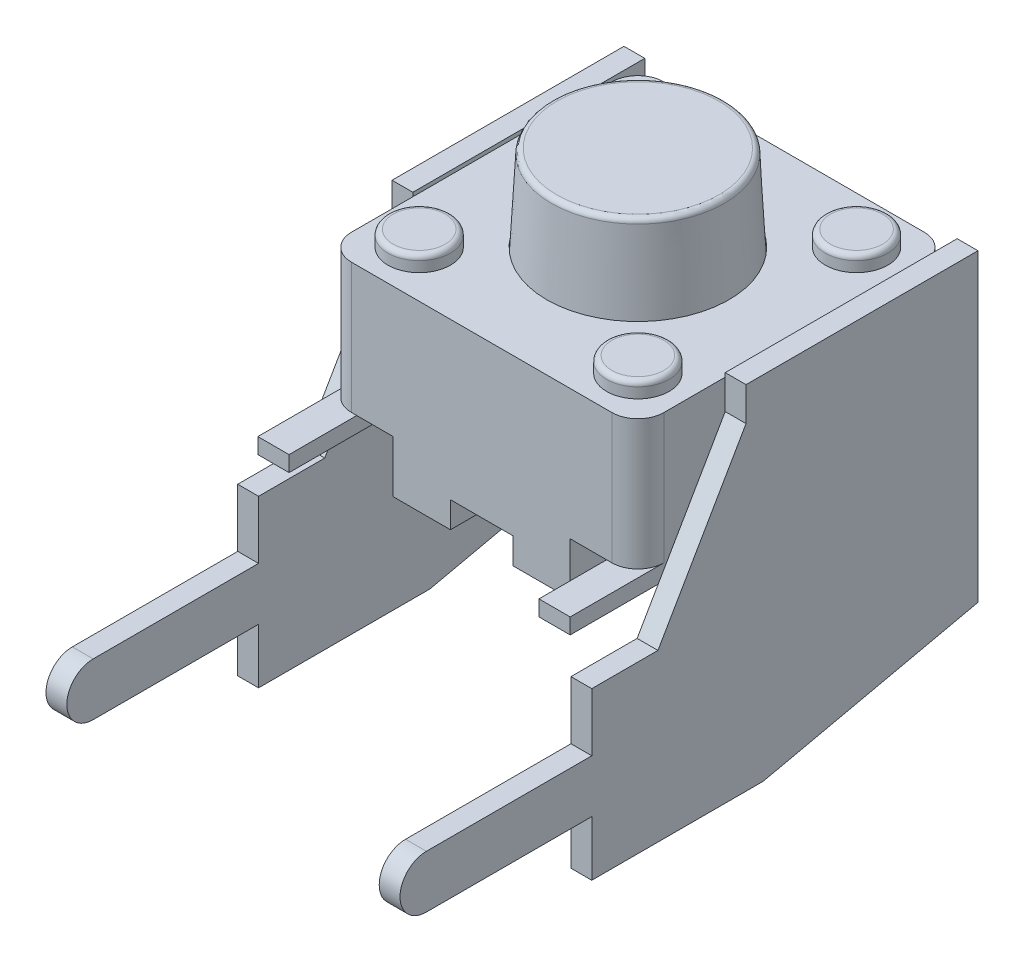
SolidWorks part; units mm, degrees
material "Custom Plastic"
ref_plane "Front Plane" through (0, 0, 0) normal (0, 0, 1) x (1, 0, 0)
ref_plane "Top Plane" through (0, 0, 0) normal (0, 1, 0) x (1, 0, 0)
ref_plane "Right Plane" through (0, 0, 0) normal (1, 0, 0) x (0, 0, -1)
sketch "Sketch1" plane through (0, 0, 0) normal (0, 1, 0) x (1, 0, 0)
  line L0 (-3.2652, 0) -> (3.207, 0) construction
  line L1 (-2.5, 3) -> (2.5, 3)
  line L2 (-3, 2.5) -> (-3, -2.5)
  line L3 (-2.5, -3) -> (2.5, -3)
  line L4 (3, 2.5) -> (3, -2.5)
  line L5 (-3, 3) -> (3, -3) construction
  line L6 (-3, -3) -> (3, 3) construction
  line L7 (0, -3.1905) -> (0, 3.2124) construction
  line L8 (3, 0) -> (2.4, 0)
  line L9 (3, 0) -> (3, -0.3)
  line L10 (3, -0.3) -> (2.4, -0.3)
  line L11 (2.4, 0) -> (2.4, -0.3)
  line L12 (-3, -0.3) -> (-2.4, -0.3)
  line L13 (-2.4, 0) -> (-2.4, -0.3)
  line L14 (-3, 0) -> (-2.4, 0)
  circle A0 centre (2.1, 2.1) radius 0.6
  circle A1 centre (2.1, -2.1) radius 0.6
  circle A2 centre (-2.1, -2.1) radius 0.6
  circle A3 centre (-2.1, 2.1) radius 0.6
  circle A4 centre (0, 0) radius 1.75
  arc A5 (2.5, 3) -> (3, 2.5) centre (2.5, 2.5) cw
  arc A6 (2.5, -3) -> (3, -2.5) centre (2.5, -2.5) ccw
  arc A7 (-3, -2.5) -> (-2.5, -3) centre (-2.5, -2.5) ccw
  arc A8 (-2.5, 3) -> (-3, 2.5) centre (-2.5, 2.5) ccw
  point P0 (0, 0)
  point P1 (0, 0)
  point P9 (0, 0)
  point P18 (0, 0)
  dimension "D1" = 6
  dimension "D2" = 0.9
  dimension "D3" = 1.2
  dimension "D5" = 3.5
  dimension "D6" = 0.5
  dimension "D7" = 0.6
  dimension "D8" = 0.3
  dimension "D4" = 4
extrude "Base" add sketch "Sketch1" along normal blind 3.3 contours L14 L2 L12 L13 | L1 A8 L2 L14 L13 L12 A7 L3 A6 L4 L10 L11 L8 A5 A0 A1 A2 A3 A4 | A3 | A2 | A4 | A1 | L8 L11 L10 L4 | A0 region at (0, 0, -2.9151) region at (-2.7, 0, 0.15) region at (2.7, 0, 0.15) region at (2.1, 0, -2.1) region at (2.1, 0, 2.1) region at (-2.1, 0, 2.1) region at (-2.1, 0, -2.1) region at (0, 0, 0)
extrude "Top Plate" add sketch "Sketch1<3>" along normal blind 0.2 from surface separate body contours L1 A8 L2 L14 L13 L12 A7 L3 A6 L4 L10 L11 L8 A5 A0 A1 A2 A3 A4 | L8 L11 L10 L4 | L14 L2 L12 L13 region at (0, 0, -2.9151) region at (-2.7, 0, 0.15) region at (2.7, 0, 0.15) starting at face at (0, 3.3, 0)
sketch "Sketch1<3>" plane through (0, 0, 0) normal (0, 1, 0) x (1, 0, 0) same geometry as "Sketch1"
extrude "Knobs" add sketch "Sketch1<4>" along normal blind 0.5 from offset 3.3 contours A1 | A2 | A3 | A0 region at (2.1, 0, -2.1) region at (2.1, 0, 2.1) region at (-2.1, 0, 2.1) region at (-2.1, 0, -2.1)
sketch "Sketch1<4>" plane through (0, 0, 0) normal (0, 1, 0) x (1, 0, 0) same geometry as "Sketch1"
extrude "Actuator" add sketch "Sketch1<5>" along normal blind 1.85 draft 3 from surface separate body contours A4 region at (0, 0, 0) starting at face at (-2.1, 3.3, -1.5)
sketch "Sketch1<5>" plane through (0, 0, 0) normal (0, 1, 0) x (1, 0, 0) same geometry as "Sketch1"
sketch "Sketch2" plane through (0, 0, 0) normal (0, -1, 0) x (1, 0, 0)
  line L0 (0, 3) -> (0.6, 3)
  line L1 (0, 3) -> (0, -3) construction
  line L2 (-2.5, 3) -> (2.5, 3) construction
  line L3 (0.6, 3) -> (1.7, 3)
  line L4 (0, -3) -> (0.6, -3)
  line L5 (-1.7, -2) -> (-3, -2)
  line L6 (0.6, -3) -> (0.6, 3)
  line L7 (-1.7, -0.9) -> (-1.7, -2)
  line L8 (-1.7, -0.9) -> (-3, -0.9)
  line L9 (1.7, -0.9) -> (3, -0.9)
  line L10 (1.7, -0.9) -> (1.7, -2)
  line L11 (-3, -0.4) -> (-1.7, -0.4)
  line L12 (-0.6, -3) -> (-0.6, 3)
  line L13 (1.7, 3) -> (1.7, -0.4)
  line L14 (-1.7, 3) -> (-1.7, -0.4)
  line L15 (3, 0) -> (-3, 0) construction
  line L16 (-3, -2.5) -> (-3, 2.5) construction
  line L21 (-2.5, -3) -> (2.5, -3) construction
  line L22 (1.7, -2) -> (3, -2)
  line L23 (3, -2.5) -> (3, 2.5) construction
  line L25 (3, -0.4) -> (1.7, -0.4)
  point P5 (0, 0)
  point P12 (0, 0)
  arc M1 (3, 2.5) -> (2.5, 3) centre (2.5, 2.5) ccw
  line M2 (2.5, 3) -> (-2.5, 3)
  arc M3 (-2.5, 3) -> (-3, 2.5) centre (-2.5, 2.5) ccw
  line M4 (-3, 2.5) -> (-3, -2.5)
  line M6 (-2.5, -3) -> (2.5, -3)
  line M8 (3, -2.5) -> (3, 2.5)
  dimension "D1" = 0.6
  dimension "D2" = 1.7
  dimension "D3" = 0.4
  dimension "D4" = 1
  dimension "D6" = 0.5
extrude "Base Leg Cutout" cut sketch "Sketch2" against normal blind 1 from surface contours L14 L11 M2 M3 M4 | L25 L13 M8 M1 M2 region at (2.3434, 0, 1.2805) region at (-2.3434, 0, 1.2805) starting at face at (0, 0, 0)
extrude "Base Shallow Cutout" cut sketch "Sketch2<3>" against normal blind 0.5 contours L1 L12 M2 M6 | L10 L22 L9 M8 | L7 L8 L5 M4 region at (2.35, 0, -1.45) region at (-2.35, 0, -1.45) region at (0, 0, 0)
sketch "Sketch2<3>" plane through (0, 0, 0) normal (0, -1, 0) x (1, 0, 0) same geometry as "Sketch2"
extrude "Pins" add sketch "Sketch1<7>" against normal blind 0.3 from offset 1 separate body contours L14 L2 L12 L13 | L8 L11 L10 L4 region at (-2.7, 0, 0.15) region at (2.7, 0, 0.15)
sketch "Sketch1<7>" plane through (0, 0, 0) normal (0, 1, 0) x (1, 0, 0) same geometry as "Sketch1"
fillet "Fillet1" radius 0.1 1 edges at (0, 5.15, 1.653)
fillet "Fillet2" radius 0.1 4 edges at (-2.1, 3.8, -1.5) (2.1, 3.8, -1.5) (-2.1, 3.8, 2.7) (2.1, 3.8, 2.7)
sketch "Sketch4" plane through (0, 0, 0.3) normal (0, 0, 1) x (1, 0, 0)
  line L4 (3, 1) -> (2.4, 1)
  line L5 (2.4, 1) -> (2.4, 0.7)
  line L6 (2.4, 0.7) -> (3, 0.7)
  line L7 (3, 0.7) -> (3, 1)
  line L8 (3, 1) -> (2.4, 1)
  line L9 (2.4, 1) -> (2.4, 0.7)
  line L10 (2.4, 0.7) -> (3, 0.7)
  line L11 (3, 0.7) -> (3, 1)
  line L12 (-2.4, 1) -> (-3, 1)
  line L13 (-3, 1) -> (-3, 0.7)
  line L14 (-3, 0.7) -> (-2.4, 0.7)
  line L15 (-2.4, 0.7) -> (-2.4, 1)
  line L16 (-2.4, 1) -> (-3, 1)
  line L17 (-3, 1) -> (-3, 0.7)
  line L18 (-3, 0.7) -> (-2.4, 0.7)
  line L19 (-2.4, 0.7) -> (-2.4, 1)
  dimension "D1" = 0
  dimension "D2" = 0
extrude "Boss-Extrude1" add sketch "Sketch4" along normal blind 4
sketch "Sketch6" plane through (3, 0, 0) normal (1, 0, 0) x (0, 0, -1)
  line L0 (3.1328, 3.575) -> (3.1328, -2.2739)
  line L1 (3.1328, -2.2739) -> (-0.9947, -3.1881)
  line L2 (-0.9947, -3.1881) -> (-4.2856, -3.1881)
  line L3 (-4.2856, -3.1881) -> (-4.2856, -2.1289)
  line L4 (-4.2856, -2.1289) -> (-7.4624, -2.1289)
  line L5 (-1.3225, 3.575) -> (-1.3225, 2.9268)
  line L6 (-7.4624, -1.117) -> (-4.2856, -1.117)
  line L7 (-4.2856, -1.117) -> (-4.2856, 0)
  line L8 (-4.2856, 0) -> (-3.0145, 0)
  line L10 (-1.3225, 3.575) -> (3.1328, 3.575)
  line L11 (-1.3225, 2.9268) -> (-3.0145, 0)
  arc A0 (-7.4624, -1.117) -> (-7.4624, -2.1289) centre (-7.4624, -1.6229) ccw
extrude "Boss-Extrude2" add sketch "Sketch6" along normal blind 0.4
sketch "Sketch7" plane through (-3, 0, 0) normal (-1, 0, 0) x (0, 0, 1)
  line L11 (1.3225, 3.575) -> (-3.1328, 3.575)
  line L12 (1.3225, 2.9268) -> (1.3225, 3.575)
  line L13 (3.0145, 0) -> (1.3225, 2.9268)
  line L14 (4.2856, 0) -> (3.0145, 0)
  line L15 (4.2856, -1.117) -> (4.2856, 0)
  line L16 (7.4624, -1.117) -> (4.2856, -1.117)
  line L17 (4.2856, -2.1289) -> (7.4624, -2.1289)
  line L18 (4.2856, -3.1881) -> (4.2856, -2.1289)
  line L19 (0.9947, -3.1881) -> (4.2856, -3.1881)
  line L20 (-3.1328, -2.2739) -> (0.9947, -3.1881)
  line L21 (-3.1328, 3.575) -> (-3.1328, -2.2739)
  line L22 (1.3225, 3.575) -> (-3.1328, 3.575)
  line L23 (1.3225, 2.9268) -> (1.3225, 3.575)
  line L24 (3.0145, 0) -> (1.3225, 2.9268)
  line L25 (4.2856, 0) -> (3.0145, 0)
  line L26 (4.2856, -1.117) -> (4.2856, 0)
  line L27 (7.4624, -1.117) -> (4.2856, -1.117)
  line L28 (4.2856, -2.1289) -> (7.4624, -2.1289)
  line L29 (4.2856, -3.1881) -> (4.2856, -2.1289)
  line L30 (0.9947, -3.1881) -> (4.2856, -3.1881)
  line L31 (-3.1328, -2.2739) -> (0.9947, -3.1881)
  line L32 (-3.1328, 3.575) -> (-3.1328, -2.2739)
  arc A1 (7.4624, -2.1289) -> (7.4624, -1.117) centre (7.4624, -1.6229) ccw
  arc A2 (7.4624, -2.1289) -> (7.4624, -1.117) centre (7.4624, -1.6229) ccw
  dimension "D1" = 0
extrude "Boss-Extrude3" add sketch "Sketch7" along normal blind 0.4
